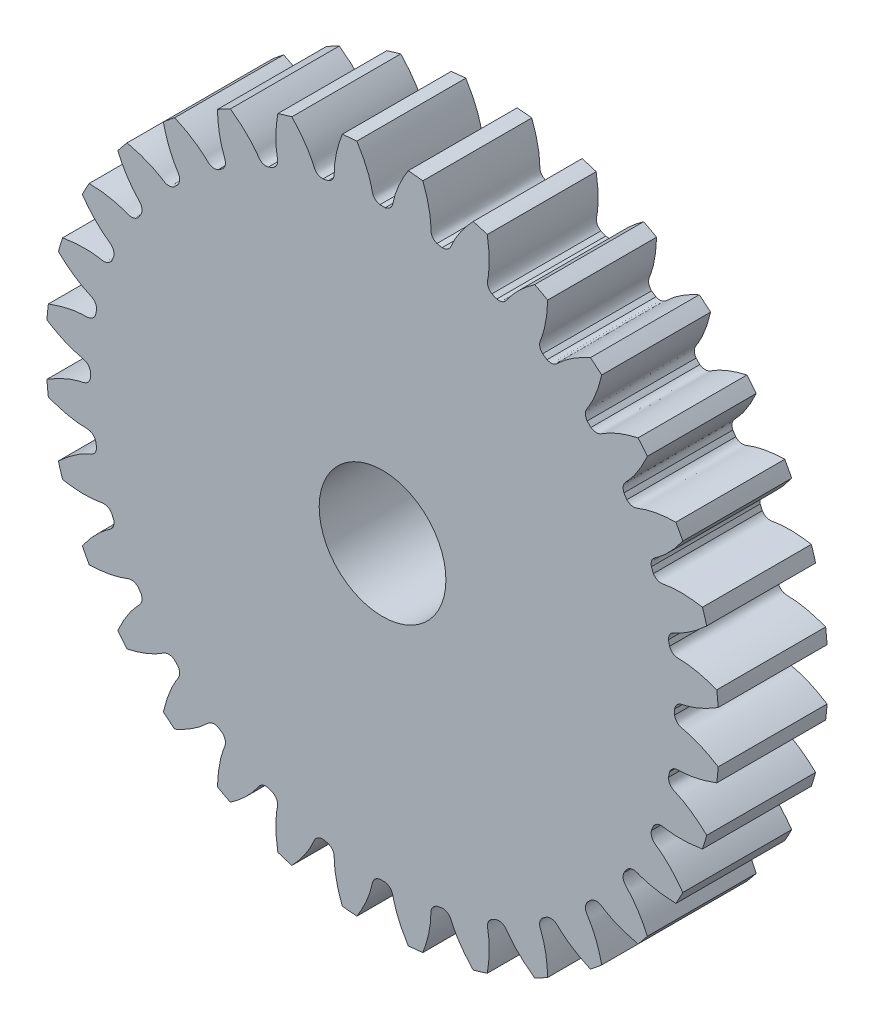
SolidWorks part; units mm, degrees
ref_plane "前视基准面" through (0, 0, 0) normal (0, 0, 1) x (1, 0, 0)
ref_plane "上视基准面" through (0, 0, 0) normal (0, 1, 0) x (1, 0, 0)
ref_plane "右视基准面" through (0, 0, 0) normal (1, 0, 0) x (0, 0, -1)
other "Configuration Table"
sketch "草图1" plane through (0, 0, 0) normal (0, 0, 1) x (1, 0, 0)
  circle A0 centre (0, 0) radius 8.5
extrude "凸台-拉伸1" add sketch "草图1" along normal blind 2.75
ref_axis "基准轴1" through (0, 0, 2.75) along (0, 0, -1)
sketch "草图2" plane through (0, 0, 0) normal (0, 0, 1) x (1, 0, 0)
  line L0 (0, 0) -> (0, 8.5) construction
  circle A0 centre (0, 0) radius 8.5 construction
  arc A1 (0.067, 7.3747) -> (-0.067, 7.3747) centre (0, 0) ccw
  arc A2 (1.6765, 9.6348) -> (-1.6765, 9.6348) centre (0, 0) ccw
  spline S0 degree 3 poles (0.067, 7.3747) (0.2444, 7.4176) (0.2542, 7.5462) (0.2867, 7.6804) (0.2952, 7.7127) (0.3051, 7.7477) (0.3166, 7.7854) (0.3299, 7.8257) (0.3449, 7.8686) (0.3618, 7.9139) (0.3807, 7.9618) (0.4017, 8.012) (0.4249, 8.0645) (0.4505, 8.1193) (0.4785, 8.1763) (0.509, 8.2353) (0.5421, 8.2964) (0.5779, 8.3594) (0.6164, 8.4243) (0.6579, 8.491) (0.7023, 8.5593) (0.7498, 8.6292) (0.8004, 8.7006) (0.8542, 8.7734) (0.9113, 8.8475) (0.9717, 8.9228) (1.0356, 8.9992) (1.1029, 9.0765) (1.1738, 9.1547) (1.2483, 9.2337) (1.3265, 9.3133) (1.4084, 9.3934) (1.5241, 9.5022) (1.6145, 9.5821) (1.6765, 9.6348) knots 0 0 0 0 0.124533 0.135329 0.147193 0.160126 0.174128 0.189198 0.205337 0.222544 0.24082 0.260164 0.280577 0.302059 0.324609 0.348227 0.372914 0.39867 0.425494 0.453386 0.482348 0.512377 0.543476 0.575642 0.608878 0.643181 0.678554 0.714995 0.752504 0.791082 0.830729 0.871444 0.913227 1 1 1 1
  spline S1 degree 3 poles (-0.067, 7.3747) (-0.2444, 7.4176) (-0.2542, 7.5462) (-0.2867, 7.6804) (-0.2952, 7.7127) (-0.3051, 7.7477) (-0.3166, 7.7854) (-0.3299, 7.8257) (-0.3449, 7.8686) (-0.3618, 7.9139) (-0.3807, 7.9618) (-0.4017, 8.012) (-0.4249, 8.0645) (-0.4505, 8.1193) (-0.4785, 8.1763) (-0.509, 8.2353) (-0.5421, 8.2964) (-0.5779, 8.3594) (-0.6164, 8.4243) (-0.6579, 8.491) (-0.7023, 8.5593) (-0.7498, 8.6292) (-0.8004, 8.7006) (-0.8542, 8.7734) (-0.9113, 8.8475) (-0.9717, 8.9228) (-1.0356, 8.9992) (-1.1029, 9.0765) (-1.1738, 9.1547) (-1.2483, 9.2337) (-1.3265, 9.3133) (-1.4084, 9.3934) (-1.5241, 9.5022) (-1.6145, 9.5821) (-1.6765, 9.6348) knots 0 0 0 0 0.124533 0.135329 0.147193 0.160126 0.174128 0.189198 0.205337 0.222544 0.24082 0.260164 0.280577 0.302059 0.324609 0.348227 0.372914 0.39867 0.425494 0.453386 0.482348 0.512377 0.543476 0.575642 0.608878 0.643181 0.678554 0.714995 0.752504 0.791082 0.830729 0.871444 0.913227 1 1 1 1
extrude "切除-拉伸1" cut sketch "草图2" along normal through all
pattern_circular "阵列(圆周)1" count 32 every 11.25 about axis through (0, 0, 2.75) along (0, 0, -1) of "切除-拉伸1"
sketch "草图3" plane through (0, 0, 0) normal (0, 0, 1) x (1, 0, 0)
  circle A0 centre (0, 0) radius 8 construction
  dimension "Dn" = 16
sketch "草图4" plane through (0, 0, 0) normal (0, 0, -1) x (-1, 0, 0)
  circle A0 centre (0, 0) radius 1.6
  dimension "D1" = 3.2
extrude "切除-拉伸2" cut sketch "草图4" against normal up to next
